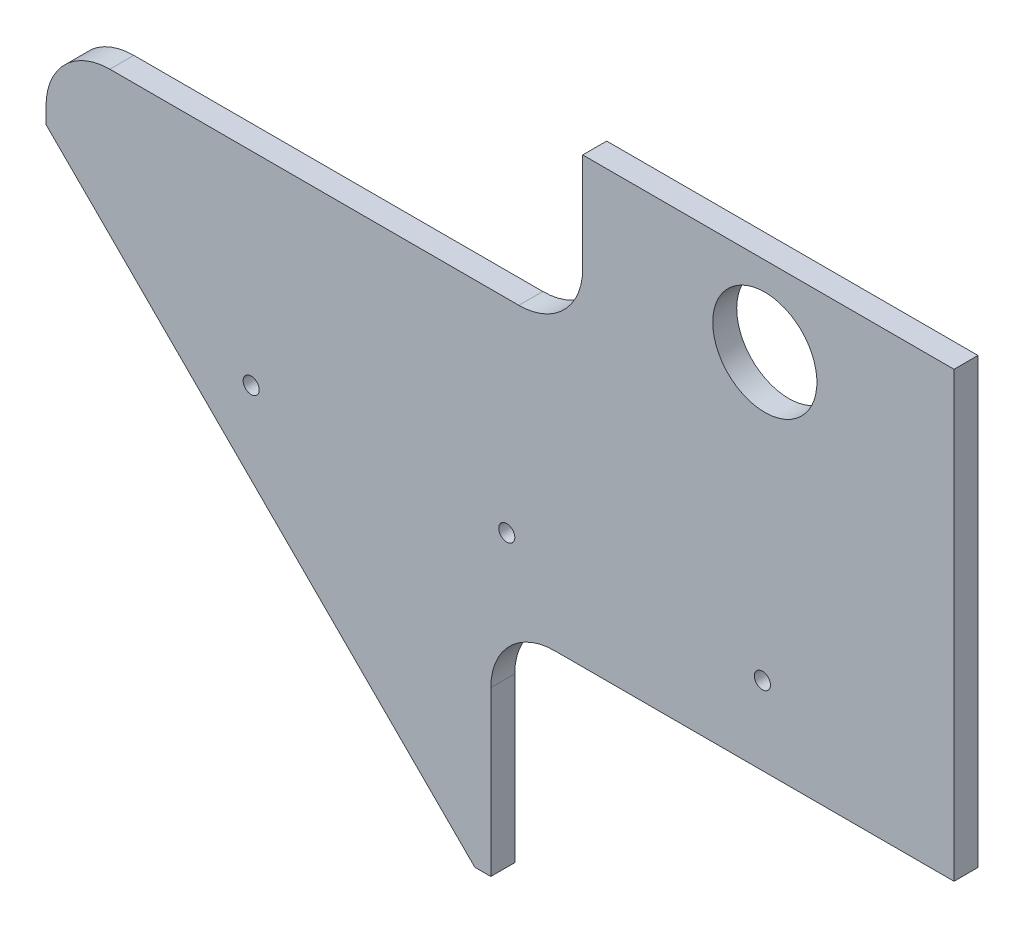
SolidWorks part; units mm, degrees
ref_plane "Front Plane" through (0, 0, 0) normal (0, 0, 1) x (1, 0, 0)
ref_plane "Top Plane" through (0, 0, 0) normal (0, 1, 0) x (1, 0, 0)
ref_plane "Right Plane" through (0, 0, 0) normal (1, 0, 0) x (0, 0, -1)
sketch "Sketch1" plane through (0, 0, 0) normal (0, 0, 1) x (1, 0, 0)
  line L0 (-138.2594, 48.9915) -> (32.2106, -121.4785)
  line L1 (32.2106, -121.4785) -> (222.7106, -121.4785)
  line L2 (-138.2594, 145.2215) -> (-138.2594, 48.9915)
  line L3 (-138.2594, 145.2215) -> (222.7106, 145.2215)
  line L4 (222.7106, -121.4785) -> (222.7106, 145.2215)
  circle A0 centre (147.4906, 113.4715) radius 20.701
  circle A2 centre (147.4906, 113.4715) radius 69.85 construction
  circle A3 centre (147.4906, 113.4715) radius 285.75 construction
  point P0 (0, 0)
  point P2 (147.4906, 113.4715)
  dimension "D4" = 234.95
  dimension "D1" = 45
  dimension "D2" = 266.7
  dimension "D5" = 247.65
extrude "Boss-Extrude1" add sketch "Sketch1" along normal blind 9.525
sketch "Sketch2" plane through (0, 0, 9.525) normal (0, 0, 1) x (1, 0, 0)
  line L0 (32.2106, -121.4785) -> (222.7106, -121.4785) construction
  line L1 (222.7106, -121.4785) -> (38.5606, -121.4785)
  line L2 (222.7106, -121.4785) -> (222.7106, -31.0571)
  line L3 (222.7106, -31.0571) -> (38.5606, -31.0571)
  line L4 (38.5606, -121.4785) -> (38.5606, -31.0571)
extrude "Cut-Extrude1" cut sketch "Sketch2" against normal through all contours L3 L4 L1 L2
fillet "Fillet1" radius 25.4 1 edges at (38.5606, -31.0571, 4.7625)
sketch "Sketch4" plane through (0, 0, 9.525) normal (0, 0, 1) x (1, 0, 0)
  line L1 (-138.2594, 145.2215) -> (-138.2594, 48.9915) construction
  line L3 (-138.2594, 145.2215) -> (75.1006, 145.2215)
  line L4 (-138.2594, 145.2215) -> (-138.2594, 80.7415)
  line L5 (-138.2594, 80.7415) -> (75.1006, 80.7415)
  line L6 (75.1006, 145.2215) -> (75.1006, 80.7415)
extrude "Cut-Extrude2" cut sketch "Sketch4" against normal through all contours L5 L6 L3 L4
fillet "Fillet2" radius 25.4 2 edges at (-138.2594, 80.7415, 4.7625) (75.1006, 80.7415, 4.7625)
hole_wizard "Ø6.4 (6.4) Diameter Hole2" positions "Sketch15" profile "Sketch14" hole size "Ø6.4" standard "Lanco STD" end condition through all
sketch "Sketch15" plane through (0, 0, 0) normal (0, 0, -1) x (-1, 0, 0)
  line L0 (-222.7106, -31.0571) -> (-222.7106, 145.2215) construction
  point P0 (-146.5106, 0)
  dimension "D1" = 76.2
sketch "Sketch14" plane through (146.5106, 0, 0) normal (1, 0, 0) x (0, 1, 0)
  line L0 (0, 0) -> (0, 9.525)
  line L1 (0, 9.525) -> (3.2, 9.525)
  line L2 (3.2, 9.525) -> (3.2, 0)
  line L5 (3.2, 0) -> (0, 0)
  line L11 (0, -6.35) -> (0, 107.95) construction
  dimension "Thru Hole Dia." = 6.4
  dimension "Thru Hole Depth" = 9.525
hole_wizard "Ø6.4 (6.4) Diameter Hole3" positions "Sketch19" profile "Sketch18" hole size "Ø6.4" standard "Lanco STD" end condition through all
sketch "Sketch19" plane through (0, 0, 0) normal (0, 0, -1) x (-1, 0, 0)
  line L0 (-222.7106, -31.0571) -> (-222.7106, 145.2215) construction
  point P0 (-44.9106, 0)
  dimension "D1" = 177.8
sketch "Sketch18" plane through (44.9106, 0, 0) normal (1, 0, 0) x (0, 1, 0)
  line L0 (0, 0) -> (0, 9.525)
  line L1 (0, 9.525) -> (3.2, 9.525)
  line L2 (3.2, 9.525) -> (3.2, 0)
  line L5 (3.2, 0) -> (0, 0)
  line L11 (0, -6.35) -> (0, 107.95) construction
  dimension "Thru Hole Dia." = 6.4
  dimension "Thru Hole Depth" = 9.525
hole_wizard "Ø6.4 (6.4) Diameter Hole4" positions "Sketch25" profile "Sketch24" hole size "Ø6.4" standard "Lanco STD" end condition through all
sketch "Sketch25" plane through (0, 0, 0) normal (0, 0, -1) x (-1, 0, 0)
  line L0 (-222.7106, -31.0571) -> (-222.7106, 145.2215) construction
  point P0 (56.6894, 0)
  dimension "D1" = 279.4
sketch "Sketch24" plane through (-56.6894, 0, 0) normal (1, 0, 0) x (0, 1, 0)
  line L0 (0, 0) -> (0, 9.525)
  line L1 (0, 9.525) -> (3.2, 9.525)
  line L2 (3.2, 9.525) -> (3.2, 0)
  line L5 (3.2, 0) -> (0, 0)
  line L11 (0, -6.35) -> (0, 107.95) construction
  dimension "Thru Hole Dia." = 6.4
  dimension "Thru Hole Depth" = 9.525
